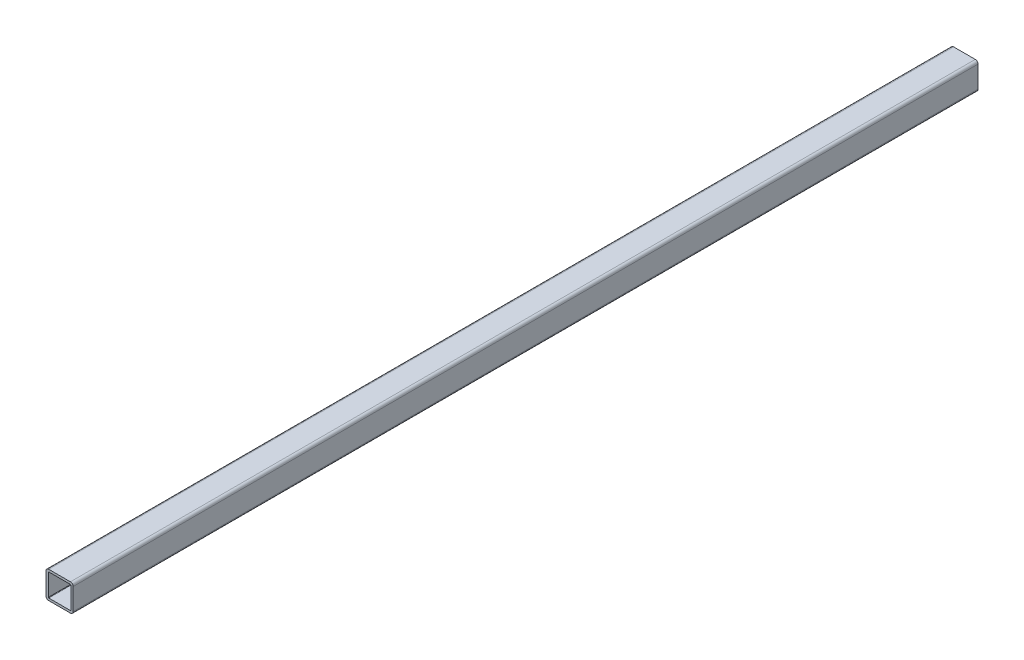
SolidWorks part; units mm, degrees
material "1060 Alloy"
ref_plane "Front Plane" through (0, 0, 0) normal (0, 0, 1) x (1, 0, 0)
ref_plane "Top Plane" through (0, 0, 0) normal (0, 1, 0) x (1, 0, 0)
ref_plane "Right Plane" through (0, 0, 0) normal (1, 0, 0) x (0, 0, -1)
sketch "Sketch1" plane through (0, 0, 0) normal (0, 0, 1) x (1, 0, 0)
  line L0 (7.9375, -7.9375) -> (9.525, -7.9375) construction
  line L1 (-9.525, -9.525) -> (9.525, -9.525)
  line L2 (-9.525, -9.525) -> (-9.525, 9.525)
  line L3 (-9.525, 9.525) -> (9.525, 9.525)
  line L4 (9.525, -9.525) -> (9.525, 9.525)
  line L5 (0, 9.525) -> (0, -9.525) construction
  line L6 (-9.525, 0) -> (9.525, 0) construction
  line L7 (-7.9375, -7.9375) -> (7.9375, -7.9375)
  line L8 (-7.9375, -7.9375) -> (-7.9375, 7.9375)
  line L9 (-7.9375, 7.9375) -> (7.9375, 7.9375)
  line L10 (7.9375, -7.9375) -> (7.9375, 7.9375)
  line L11 (0, 7.9375) -> (0, -7.9375) construction
  line L12 (-7.9375, 0) -> (7.9375, 0) construction
  point P0 (0, 0)
  point P4 (0, 0)
  dimension "Outside Height" = 19.05
  dimension "Outside Width" = 19.05
  dimension "Inside Height" = 15.875
  dimension "Inside Width" = 15.875
  dimension "Wall Thickness" = 1.5875
sketch "Sketch3" plane through (0, 0, 0) normal (1, 0, 0) x (0, 0, -1)
  line L0 (-317.5, -9.525) -> (317.5, -9.525) construction
  point P2 (-292.1, -9.525)
  point P4 (292.1, -9.525)
  dimension "Length" = 635
  dimension "D2" = 25.4
sketch "Sketch2" plane through (0, 0, 0) normal (0, 0, 1) x (1, 0, 0)
  line L0 (-7.9375, -7.9375) -> (-7.9375, 7.9375) construction
  line L1 (-7.9375, -7.9375) -> (7.9375, -7.9375) construction
  line L2 (7.9375, -7.9375) -> (7.9375, 7.9375) construction
  line L3 (-7.9375, 7.9375) -> (7.9375, 7.9375) construction
  line L4 (-7.9375, -7.9375) -> (-7.9375, 7.9375)
  line L5 (-7.9375, -7.9375) -> (7.9375, -7.9375)
  line L6 (7.9375, -7.9375) -> (7.9375, 7.9375)
  line L7 (-7.9375, 7.9375) -> (7.9375, 7.9375)
  line L8 (-9.525, -9.525) -> (-9.525, 9.525) construction
  line L9 (-9.525, -9.525) -> (9.525, -9.525) construction
  line L10 (9.525, -9.525) -> (9.525, 9.525) construction
  line L11 (-9.525, 9.525) -> (9.525, 9.525) construction
  line L12 (-9.525, -9.525) -> (-9.525, 9.525)
  line L13 (-9.525, -9.525) -> (9.525, -9.525)
  line L14 (9.525, -9.525) -> (9.525, 9.525)
  line L15 (-9.525, 9.525) -> (9.525, 9.525)
extrude "Boss-Extrude1" add sketch "Sketch2" along normal mid plane 635
fillet "Fillet1" radius 1.905 4 edges at (-9.525, -9.525, 0) (-9.525, 9.525, 0) (9.525, -9.525, 0) (9.525, 9.525, 0)
fillet "Fillet2" radius 0.3175 4 edges at (7.9375, 7.9375, 0) (7.9375, -7.9375, 0) (-7.9375, -7.9375, 0) (-7.9375, 7.9375, 0)
equation "\"D1@Boss-Extrude1\"=\"length@sketch3\""
equation "\"D1@Fillet1\"=\"Wall Thickness@Sketch1\"*1.2"
equation "\"D1@Fillet2\"=\"D1@Fillet1\"-\"Wall Thickness@Sketch1\""
equation "\"D2@Sketch3\"=\"D1@Sketch3\""
